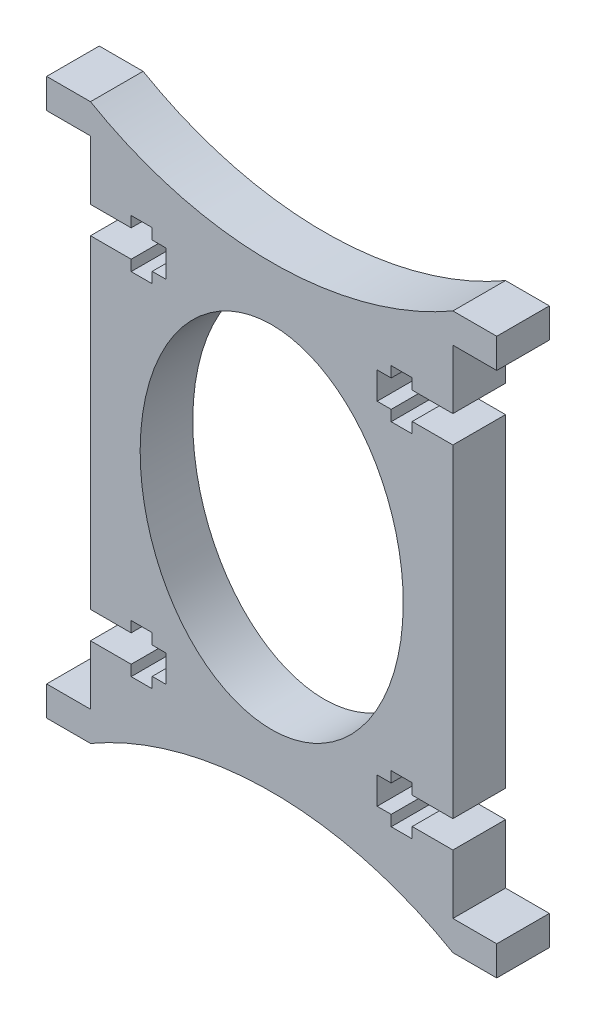
SolidWorks part; units mm, degrees
material "Acrylic (Medium-high impact)"
ref_plane "Front Plane" through (0, 0, 0) normal (0, 0, 1) x (1, 0, 0)
ref_plane "Top Plane" through (0, 0, 0) normal (0, 1, 0) x (1, 0, 0)
ref_plane "Right Plane" through (0, 0, 0) normal (1, 0, 0) x (0, 0, -1)
sketch "Sketch1" plane through (0, 0, 0) normal (0, 0, 1) x (1, 0, 0)
  line L0 (742.183, 459.4261) -> (700.8541, 459.4261) construction
  line L1 (737.5448, 439.4261) -> (742.1973, 439.4261) construction
  line L2 (737.5448, 439.4261) -> (737.5448, 437.8782) construction
  line L3 (737.5448, 440.9739) -> (737.5448, 439.4261) construction
  line L4 (736.3448, 436.6538) -> (736.3448, 439.4261) construction
  line L5 (733.5448, 439.4261) -> (742.1973, 439.4261) construction
  line L6 (736.3448, 442.1983) -> (736.3448, 439.4261) construction
  line L7 (735.1448, 436.6538) -> (737.5448, 436.6538)
  line L8 (700.8541, 459.4261) -> (700.8541, 440.9739)
  line L9 (706.6923, 442.1983) -> (706.6923, 439.4261) construction
  line L10 (735.1448, 442.1983) -> (737.5448, 442.1983)
  line L11 (733.5448, 440.9739) -> (733.5448, 437.8782)
  line L12 (742.183, 437.8782) -> (742.183, 431.1161)
  line L13 (742.183, 437.8782) -> (737.5448, 437.8782)
  line L14 (737.5448, 440.9739) -> (742.183, 440.9739)
  line L15 (747.183, 427.7361) -> (747.183, 431.1161)
  line L16 (742.183, 427.7361) -> (747.183, 427.7361)
  line L17 (709.4923, 439.4261) -> (700.8541, 439.4261) construction
  line L18 (707.8923, 436.6538) -> (707.8923, 437.8782)
  line L19 (707.8923, 440.9739) -> (709.4923, 440.9739)
  line L20 (707.8923, 437.8782) -> (709.4923, 437.8782)
  line L21 (707.8923, 440.9739) -> (707.8923, 442.1983)
  line L22 (706.6923, 436.6538) -> (706.6923, 439.4261) construction
  line L23 (705.4923, 436.6538) -> (705.4923, 437.8782)
  line L24 (705.4923, 440.9739) -> (705.4923, 442.1983)
  line L25 (705.4923, 440.9739) -> (705.4923, 439.4261) construction
  line L26 (705.4923, 439.4261) -> (705.4923, 437.8782) construction
  line L27 (695.8541, 431.1161) -> (700.8541, 431.1161)
  line L28 (700.8541, 427.7361) -> (695.8541, 427.7361)
  line L29 (695.8541, 427.7361) -> (695.8541, 431.1161)
  line L30 (705.4923, 440.9739) -> (700.8541, 440.9739)
  line L31 (700.8541, 437.8782) -> (705.4923, 437.8782)
  line L32 (700.8541, 437.8782) -> (700.8541, 431.1161)
  line L33 (705.4923, 439.4261) -> (700.8541, 439.4261) construction
  line L34 (709.4923, 440.9739) -> (709.4923, 437.8782)
  line L35 (747.183, 431.1161) -> (742.183, 431.1161)
  line L36 (737.5448, 440.9739) -> (737.5448, 442.1983)
  line L37 (737.5448, 436.6538) -> (737.5448, 437.8782)
  line L38 (735.1448, 440.9739) -> (735.1448, 442.1983)
  line L39 (735.1448, 437.8782) -> (733.5448, 437.8782)
  line L40 (735.1448, 440.9739) -> (733.5448, 440.9739)
  line L41 (735.1448, 436.6538) -> (735.1448, 437.8782)
  line L42 (742.183, 459.4261) -> (742.183, 440.9739)
  line L43 (705.4923, 479.4261) -> (700.8541, 479.4261) construction
  line L44 (707.8923, 442.1983) -> (705.4923, 442.1983)
  line L45 (705.4923, 479.4261) -> (705.4923, 480.9739) construction
  line L46 (705.4923, 477.8782) -> (705.4923, 479.4261) construction
  line L47 (706.6923, 482.1983) -> (706.6923, 479.4261) construction
  line L48 (709.4923, 479.4261) -> (700.8541, 479.4261) construction
  line L49 (706.6923, 476.6538) -> (706.6923, 479.4261) construction
  line L50 (736.3448, 476.6538) -> (736.3448, 479.4261) construction
  line L51 (733.5448, 479.4261) -> (742.1973, 479.4261) construction
  line L52 (736.3448, 482.1983) -> (736.3448, 479.4261) construction
  line L53 (737.5448, 477.8782) -> (737.5448, 479.4261) construction
  line L54 (737.5448, 479.4261) -> (737.5448, 480.9739) construction
  line L55 (737.5448, 479.4261) -> (742.1973, 479.4261) construction
  line L56 (707.8923, 482.1983) -> (705.4923, 482.1983)
  line L57 (707.8923, 476.6538) -> (705.4923, 476.6538)
  line L58 (742.183, 459.4261) -> (742.183, 477.8782)
  line L59 (735.1448, 482.1983) -> (735.1448, 480.9739)
  line L60 (721.5185, -540.5739) -> (721.5185, 49459.4261) construction
  line L61 (707.8923, 436.6538) -> (705.4923, 436.6538)
  line L62 (735.1448, 477.8782) -> (733.5448, 477.8782)
  line L63 (735.1448, 480.9739) -> (733.5448, 480.9739)
  line L64 (735.1448, 477.8782) -> (735.1448, 476.6538)
  line L65 (737.5448, 482.1983) -> (737.5448, 480.9739)
  line L66 (737.5448, 477.8782) -> (737.5448, 476.6538)
  line L67 (747.183, 487.7361) -> (742.183, 487.7361)
  line L68 (709.4923, 477.8782) -> (709.4923, 480.9739)
  line L69 (700.8541, 480.9739) -> (700.8541, 487.7361)
  line L70 (700.8541, 480.9739) -> (705.4923, 480.9739)
  line L71 (705.4923, 477.8782) -> (700.8541, 477.8782)
  line L72 (695.8541, 491.1161) -> (695.8541, 487.7361)
  line L73 (700.8541, 491.1161) -> (695.8541, 491.1161)
  line L74 (695.8541, 487.7361) -> (700.8541, 487.7361)
  line L75 (705.4923, 477.8782) -> (705.4923, 476.6538)
  line L76 (705.4923, 482.1983) -> (705.4923, 480.9739)
  line L77 (707.8923, 477.8782) -> (707.8923, 476.6538)
  line L78 (707.8923, 480.9739) -> (709.4923, 480.9739)
  line L79 (707.8923, 477.8782) -> (709.4923, 477.8782)
  line L80 (707.8923, 482.1983) -> (707.8923, 480.9739)
  line L81 (742.183, 491.1161) -> (747.183, 491.1161)
  line L82 (747.183, 491.1161) -> (747.183, 487.7361)
  line L83 (737.5448, 477.8782) -> (742.183, 477.8782)
  line L84 (742.183, 480.9739) -> (737.5448, 480.9739)
  line L85 (742.183, 480.9739) -> (742.183, 487.7361)
  line L86 (733.5448, 477.8782) -> (733.5448, 480.9739)
  line L87 (735.1448, 476.6538) -> (737.5448, 476.6538)
  line L88 (700.8541, 459.4261) -> (700.8541, 477.8782)
  line L89 (735.1448, 482.1983) -> (737.5448, 482.1983)
  line L90 (721.5185, 459.4261) -> (706.5185, 459.4261) construction
  line L91 (700.8541, 480.9739) -> (700.8541, 477.8782) construction
  line L92 (700.8541, 487.7361) -> (700.8541, 491.1161) construction
  line L93 (700.8541, 431.1161) -> (700.8541, 427.7361) construction
  line L94 (700.8541, 491.1161) -> (742.183, 491.1161) construction
  line L95 (700.8541, 427.7361) -> (742.183, 427.7361) construction
  arc A0 (700.8541, 491.1161) -> (742.183, 491.1161) centre (721.5185, 526.8562) ccw
  arc A1 (700.8541, 427.7361) -> (742.183, 427.7361) centre (721.5185, 391.996) cw
  ellipse E0 centre (721.5185, 459.4261) end of major axis (721.5185, 479.4261) minor radius 15
  point P38 (721.5185, 459.4261)
  point P102 (700.8541, 489.4261)
  point P103 (700.8541, 429.4261)
  dimension "D1" = 60
  dimension "D2" = 3.0957
  dimension "D3" = 3.38
  dimension "D4" = 10
  dimension "D5" = 1.6
  dimension "D7" = 2.4
  dimension "D8" = 1.2244
  dimension "D10" = 5
  dimension "D12" = 30
  dimension "D13" = 40
  dimension "D14" = 5.6644
  dimension "D15" = 4.6382
extrude "Boss-Extrude1" add sketch "Sketch1" along normal blind 6
